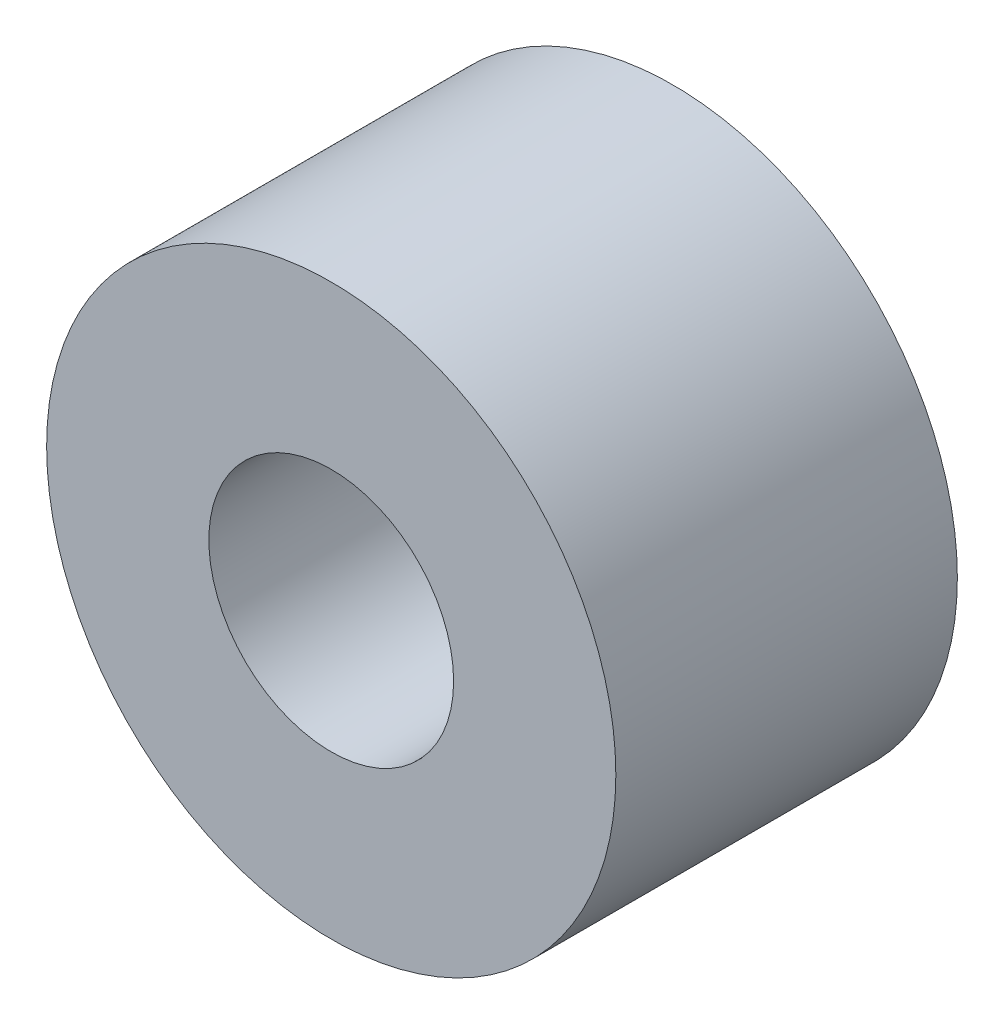
SolidWorks part; units mm, degrees
ref_plane "Front Plane" through (0, 0, 0) normal (0, 0, 1) x (1, 0, 0)
ref_plane "Top Plane" through (0, 0, 0) normal (0, 1, 0) x (1, 0, 0)
ref_plane "Right Plane" through (0, 0, 0) normal (1, 0, 0) x (0, 0, -1)
sketch "Sketch3" plane through (0, 0, 0) normal (0, 0, 1) x (1, 0, 0)
  circle A0 centre (0, 0) radius 2.15 construction
  circle A1 centre (0, 0) radius 5 construction
  point P6 (0, -2.15)
  dimension "OD" = 10
  dimension "ID" = 4.3
sketch "Sketch1" plane through (0, 0, 0) normal (1, 0, 0) x (0, 0, -1)
  line L0 (-3, -2.15) -> (-3, 2.15) construction
  line L1 (3, -5) -> (-3, -5) construction
  line L2 (3, -5) -> (3, 5) construction
  line L3 (3, 5) -> (-3, 5) construction
  line L4 (-3, -5) -> (-3, 5) construction
  line L5 (0, 5) -> (0, -5) construction
  line L6 (3, 0) -> (-3, 0) construction
  line L8 (0, 5) -> (0, -5) construction
  line L9 (-3, 2.15) -> (0, 2.15) construction
  point P0 (0, 0)
  point P7 (-3, 0)
  dimension "Length" = 6
sketch "Sketch2" plane through (0, 0, 0) normal (0, 0, 1) x (1, 0, 0)
  circle A0 centre (0, 0) radius 5
  circle A1 centre (0, 0) radius 2.15
extrude "Extrude1" add sketch "Sketch2" along normal up to vertex and the other way up to vertex up to point (0, -5, 3) other way up to point (0, 5, -3)
